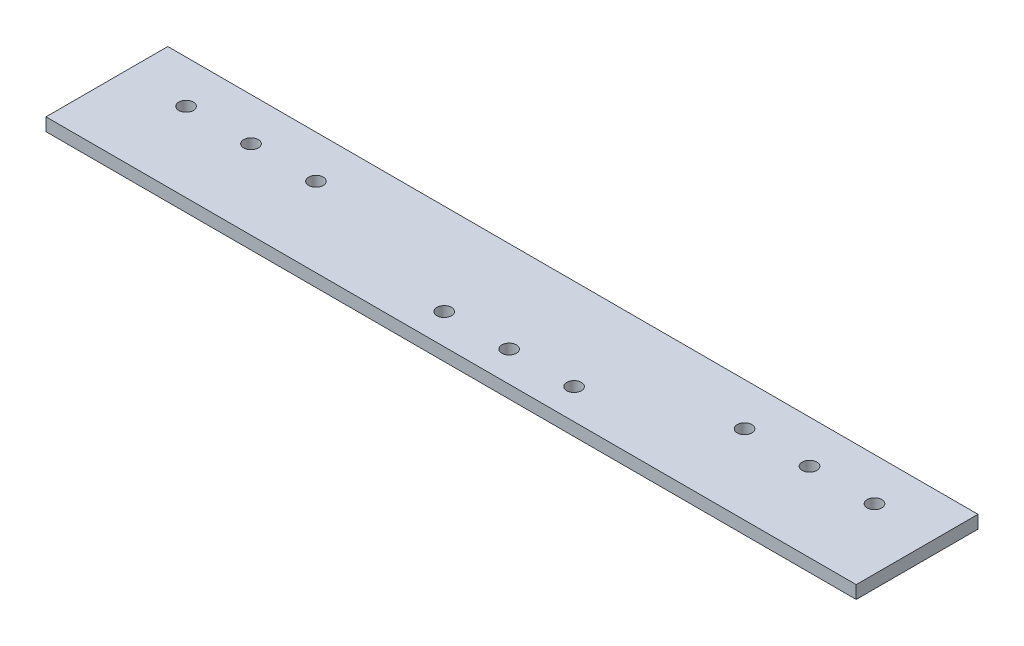
SolidWorks part; units mm, degrees
ref_plane "Front" through (0, 0, 0) normal (0, 0, 1) x (1, 0, 0)
ref_plane "Top" through (0, 0, 0) normal (0, 1, 0) x (1, 0, 0)
ref_plane "Right" through (0, 0, 0) normal (1, 0, 0) x (0, 0, -1)
sketch "Sketch1" plane through (0, 0, 0) normal (0, 1, 0) x (1, 0, 0)
  line L1 (0, 0) -> (199.58, 0)
  line L2 (0, 0) -> (0, 30)
  line L3 (0, 30) -> (199.58, 30)
  line L4 (199.58, 0) -> (199.58, 30)
  dimension "D1" = 199.58
  dimension "D2" = 30
extrude "Boss-Extrude1" add sketch "Sketch1" along normal blind 3.175
sketch "Sketch2" plane through (0, 3.175, 0) normal (0, 1, 0) x (1, 0, 0)
  circle A0 centre (47, 19.5) radius 1.8
  circle A1 centre (31, 19.5) radius 1.8
  circle A2 centre (15, 19.5) radius 1.8
  circle A3 centre (90.58, 7.5) radius 1.8
  circle A4 centre (106.58, 7.5) radius 1.8
  circle A6 centre (168.58, 19.5) radius 1.8
  circle A7 centre (184.58, 19.5) radius 1.8
  circle A8 centre (152.58, 19.5) radius 1.8
  circle A9 centre (122.58, 7.5) radius 1.8
extrude "Cut-Extrude1" cut sketch "Sketch2" against normal blind 5
